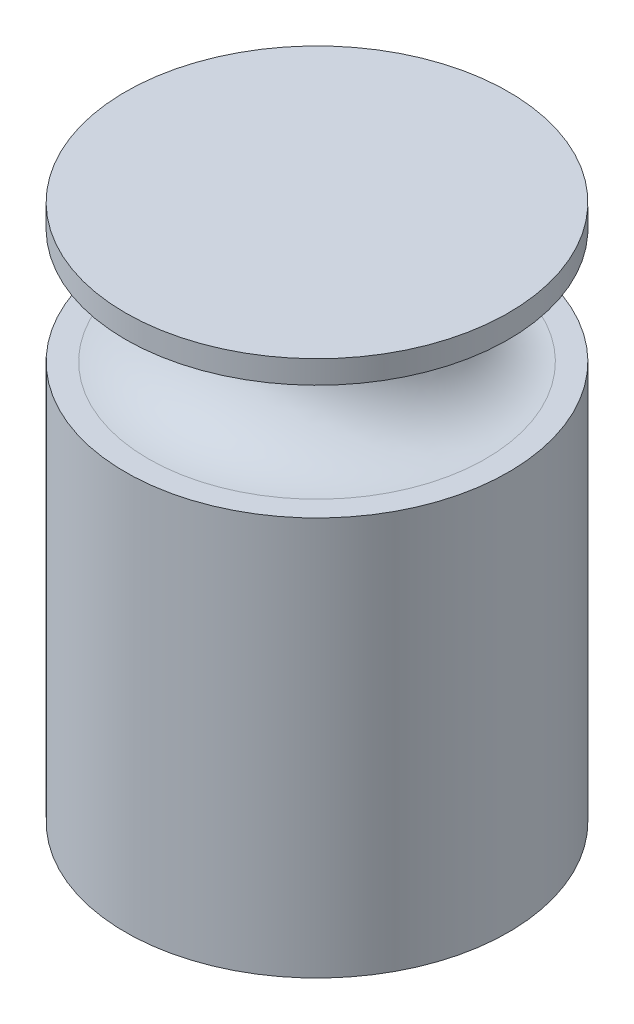
SolidWorks part; units mm, degrees
ref_plane "Front Plane" through (0, 0, 0) normal (0, 0, 1) x (1, 0, 0)
ref_plane "Top Plane" through (0, 0, 0) normal (0, 1, 0) x (1, 0, 0)
ref_plane "Right Plane" through (0, 0, 0) normal (1, 0, 0) x (0, 0, -1)
sketch "Sketch1" plane through (0, 0, 0) normal (0, 1, 0) x (1, 0, 0)
  circle A0 centre (0, 0) radius 25
extrude "Boss-Extrude1" add sketch "Sketch1" along normal blind 52
sketch "Sketch2" plane through (0, 52, 0) normal (0, 1, 0) x (1, 0, 0)
  circle A0 centre (0, 0) radius 12
extrude "Boss-Extrude2" add sketch "Sketch2" along normal blind 15
sketch "Sketch3" plane through (0, 67, 0) normal (0, 1, 0) x (1, 0, 0)
  circle A0 centre (0, 0) radius 25
extrude "Boss-Extrude3" add sketch "Sketch3" along normal blind 3
fillet "Fillet1" radius 10 1 edges at (0, 52, 12)
fillet "Fillet2" radius 10 1 edges at (0, 67, 12)
sketch "Sketch4" plane through (0, 0, 0) normal (0, -1, 0) x (-1, 0, 0)
  circle A0 centre (0, 0) radius 20
extrude "Cut-Extrude1" cut sketch "Sketch4" against normal blind 18
